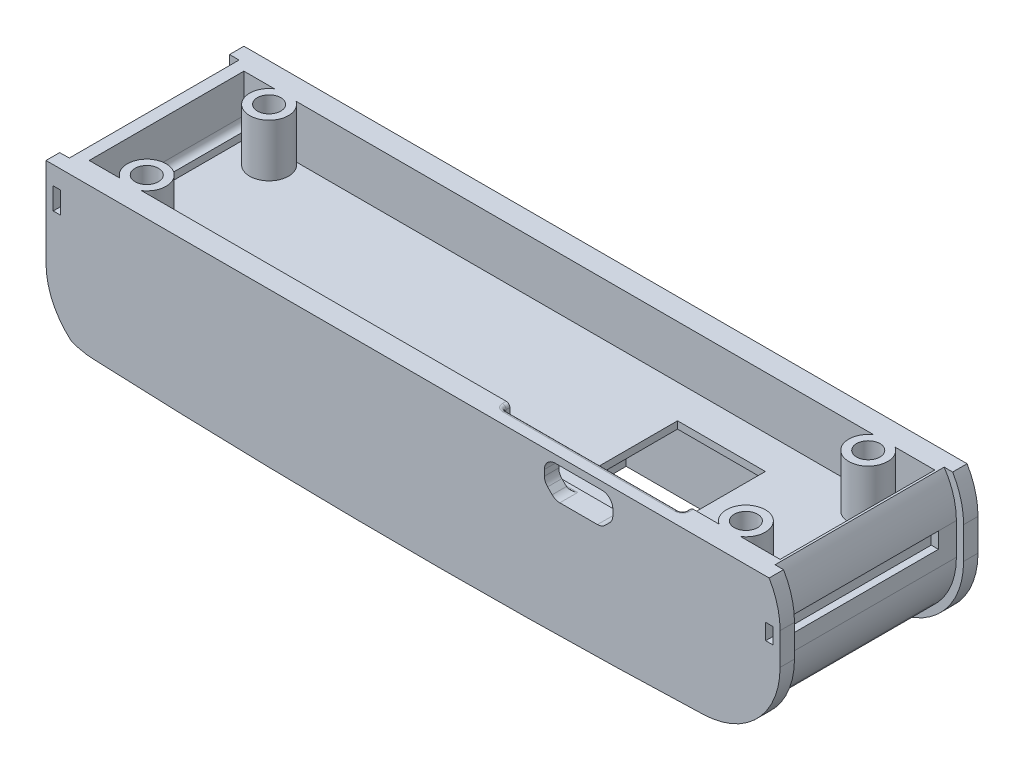
SolidWorks part; units mm, degrees
material "ABS"
ref_plane "Front" through (0, 0, 0) normal (0, 0, 1) x (1, 0, 0)
ref_plane "Top" through (0, 0, 0) normal (0, 1, 0) x (1, 0, 0)
ref_plane "Right" through (0, 0, 0) normal (1, 0, 0) x (0, 0, -1)
sketch "草图1" plane through (0, 0, 0) normal (0, 1, 0) x (1, 0, 0)
  line L0 (-48, 10.75) -> (-50, 10.75) construction
  line L6 (-48, 9.7892) -> (-48, -9.7108)
  line L12 (48, 9.7892) -> (48, -9.7108)
  line L13 (-48, 10.75) -> (48, -10.75) construction
  line L14 (-48, -10.75) -> (43.5349, 9.75) construction
  line L15 (-50, 12.75) -> (50, 12.75)
  line L16 (-50, 12.75) -> (-50, -12.75)
  line L17 (-50, -12.75) -> (50, -12.75)
  line L18 (50, 12.75) -> (50, -12.75)
  line L19 (-50, 12.75) -> (50, -12.75) construction
  line L20 (-50, -12.75) -> (-38.2259, -9.7476) construction
  line L21 (-48, 10.75) -> (-48, 12.75) construction
  line L24 (-48, 9.7892) -> (-48, 10.75)
  line L25 (-48, 10.75) -> (45.2523, 10.75)
  line L26 (45.2523, -13.75) -> (45.2523, 13.75) construction
  line L27 (48, 10.75) -> (-48, 10.75) construction
  line L29 (-48, -9.7108) -> (-48, -10.75)
  line L30 (-48, -10.75) -> (48, -10.75)
  line L31 (48, -10.75) -> (48, -9.7108)
  line L32 (0, 0) -> (42.1569, 10.75) construction
  line L33 (45.2523, 10.75) -> (48, 10.75)
  line L34 (48, 10.75) -> (48, 9.7892)
  point P0 (0, 0)
  point P6 (0, 0)
  dimension "D3" = 96
extrude "凸台-拉伸1" add sketch "草图1" along normal blind 13.2
sketch "草图2" plane through (0, 13.2, 0) normal (0, 1, 0) x (1, 0, 0)
  line L0 (-48, 0) -> (-23, 0) construction
  line L1 (-48, 10.75) -> (48, 10.75)
  line L2 (-48, 10.75) -> (-48, -10.75)
  line L3 (-48, -10.75) -> (48, -10.75)
  line L4 (48, 10.75) -> (48, -10.75)
  line L5 (-48, 10.75) -> (48, -10.75) construction
  line L6 (-48, -10.75) -> (48, 10.75) construction
  line L7 (17, 6) -> (29, 6)
  line L8 (17, 6) -> (17, -6)
  line L9 (17, -6) -> (29, -6)
  line L10 (29, 6) -> (29, -6)
  line L11 (-6, 6) -> (6, -6) construction
  line L12 (-6, -6) -> (6, 6) construction
  line L13 (0, 0) -> (23, 0) construction
  point P0 (0, 0)
  point P7 (0, 0)
  point P8 (0, 0)
  dimension "D1" = 12
extrude "凸台-拉伸2" add sketch "草图2" against normal blind 2
sketch "草图3" plane through (0, 13.2, 0) normal (0, 1, 0) x (1, 0, 0)
  line L0 (0, 0) -> (-50, 0) construction
  line L1 (-50, 12.75) -> (-50, -12.75) construction
  line L2 (-50, -12.75) -> (-50, 12.75)
  line L3 (-50, 12.75) -> (50, 12.75)
  line L4 (50, 12.75) -> (50, -0.0404)
  line L5 (50, -12.75) -> (50, 12.75) construction
  line L7 (48, 0.0137) -> (48, 10.75)
  line L8 (48, 10.75) -> (-48, 10.75)
  line L9 (-48, 10.75) -> (-48, -10.75)
  line L10 (48, -10.75) -> (-48, -10.75)
  line L11 (48, 0.0137) -> (48, -10.75)
  line L13 (50, -12.75) -> (50, -0.0404)
  line L14 (-50, -12.75) -> (50, -12.75)
  line L15 (48, 10.75) -> (-48, 10.75) construction
  line L16 (-48, 10.75) -> (-48, -10.75) construction
  line L17 (48, -10.75) -> (48, 10.75) construction
  point P17 (-48, 0)
extrude "凸台-拉伸3" add sketch "草图3" along normal blind 6.3
sketch "草图6" plane through (0, 19.5, 0) normal (0, 1, 0) x (1, 0, 0)
  line L6 (0, 0) -> (0, -19.5291) construction
  line L7 (-23, 6) -> (41, 6) construction
  line L8 (-32.25, -8.5) -> (29.1938, -8.5) construction
  line L9 (-32.25, 8.5) -> (39.5985, 8.5) construction
  line L10 (-50, 0) -> (0, 0) construction
  circle A4 centre (41, 8.5) radius 2.7
  circle A5 centre (41, -8.5) radius 2.7
  circle A6 centre (-42.25, -8.5) radius 2.7
  circle A7 centre (-42.25, 8.5) radius 2.7
extrude "凸台-拉伸4" add sketch "草图6" against normal up to next
sketch "草图7" plane through (0, 19.5, 0) normal (0, 1, 0) x (1, 0, 0)
  line L0 (0, 12.75) -> (0, 0) construction
  line L1 (0, 0) -> (-50, 0) construction
  line L4 (50, 12.75) -> (-50, 12.75) construction
  circle A4 centre (41, 8.5) radius 1.625
  circle A5 centre (41, -8.5) radius 1.625
  circle A6 centre (-42.25, -8.5) radius 1.625
  circle A7 centre (-42.25, 8.5) radius 1.625
  dimension "D1" = 83.25
extrude "切除-拉伸3" cut sketch "草图7" against normal blind 5.5
sketch "草图10" plane through (0, 11.2, 0) normal (0, -1, 0) x (1, 0, 0)
  line L0 (-23, 0) -> (23, 0) construction
  line L1 (15.9, 7.1) -> (30.1, 7.1)
  line L2 (15.9, 7.1) -> (15.9, -7.1)
  line L3 (15.9, -7.1) -> (30.1, -7.1)
  line L4 (30.1, 7.1) -> (30.1, -7.1)
  line L5 (15.9, 7.1) -> (30.1, -7.1) construction
  line L6 (15.9, -7.1) -> (30.1, 7.1) construction
  line L7 (15.1, 7.9) -> (30.9, 7.9)
  line L8 (15.1, 7.9) -> (15.1, -7.9)
  line L9 (15.1, -7.9) -> (30.9, -7.9)
  line L10 (30.9, 7.9) -> (30.9, -7.9)
  line L11 (15.1, 7.9) -> (30.9, -7.9) construction
  line L12 (15.1, -7.9) -> (30.9, 7.9) construction
  point P0 (23, 0)
  dimension "D1" = 14.2
  dimension "D2" = 0.8
extrude "凸台-拉伸5" add sketch "草图10" along normal blind 0.8 contours L10 L7 L8 L9 L1 L4 L3 L2 region at (23, 11.2, 7.6766)
sketch "草图11" plane through (0, 0, 12.75) normal (0, 0, 1) x (1, 0, 0)
  line L0 (0, 0) -> (0, 19.5) construction
  line L1 (-4, 17.65) -> (4, 17.65)
  line L2 (4, 17.65) -> (4, 15.8)
  line L3 (4, 15.8) -> (3, 14.8)
  line L4 (3, 14.8) -> (-3, 14.8)
  line L5 (-4, 15.8) -> (-3, 14.8)
  line L6 (-4, 17.65) -> (-4, 15.8)
  line L7 (-50, 19.5) -> (50, 19.5) construction
  line L8 (-39.5075, 13.2) -> (30.7575, 13.2) construction
  point P7 (0, 14.8)
  point P9 (0, 17.65)
  dimension "D1" = 8
  dimension "D2" = 135
  dimension "D3" = 1
  dimension "D4" = 1.6
  dimension "D5" = 2.85
extrude "切除-拉伸5" cut sketch "草图11" against normal blind 3
fillet "圆角6" radius 0.5 6 edges at (4, 15.8, 11.75) (3, 14.8, 11.75) (-3, 14.8, 11.75) (-4, 15.8, 11.75) (-4, 17.65, 11.75) (4, 17.65, 11.75)
fillet "圆角3" radius 0.95 2 edges at (-48, 13.2, 0) (48, 13.2, 0)
fillet "圆角1" radius 2 4 edges at (50, 9.75, -12.75) (-50, 9.75, 12.75) (50, 9.75, 12.75) (-50, 9.75, -12.75)
ref_plane "基准面3" through (0, 0, -10.75) normal (0, 0, -1) x (-1, 0, 0)
sketch "草图23" plane through (0, 0, -10.75) normal (0, 0, -1) x (-1, 0, 0)
  line L0 (-50, 19.5) -> (-50, -0.5)
  line L5 (-48, 19.5) -> (-50, 19.5) construction
  line L6 (-50, -0.5) -> (51, -0.5)
  line L7 (51, -0.5) -> (51, 19.5)
  line L8 (51, 19.5) -> (-50, 19.5)
sketch "草图18" plane through (0, 19.5, 0) normal (0, 1, 0) x (1, 0, 0)
  line L0 (-48, -12.75) -> (-53, -12.75)
  line L1 (-53, 26) -> (-53, -26) construction
  line L2 (-53, -12.75) -> (-53, -11.8645)
  line L6 (-37.0111, -11.75) -> (-37.0111, -12.75)
  line L7 (-48, -12.75) -> (48, -12.75) construction
  line L8 (-37.0111, -12.75) -> (-48, -12.75)
  line L9 (-37.0111, 11.75) -> (-37.0111, 12.75)
  line L11 (48, 12.75) -> (-48, 12.75) construction
  line L12 (-37.0111, 12.75) -> (-53, 12.75)
  line L13 (-53, 12.75) -> (-53, 11.75)
  line L15 (-53, -11.8645) -> (-37.0111, -11.75)
  line L16 (-53, 11.75) -> (-37.0111, 11.75)
extrude "凸台-拉伸7" add sketch "草图18" against normal blind 20
sketch "草图19" plane through (-53, 0, 0) normal (-1, 0, 0) x (0, 0, 1)
  line L0 (11.8736, -0.5079) -> (26.8736, -0.5079)
  line L1 (26.8736, -0.5079) -> (26.8736, 19.4921)
  line L2 (26.8736, 19.4921) -> (11.8736, 19.4921)
  line L3 (11.8736, 19.4921) -> (11.8736, -0.5079)
  line L4 (-11.75, -0.5) -> (-26.75, -0.5)
  line L5 (-12.75, -0.5) -> (-11.75, -0.5) construction
  line L6 (-11.75, -0.5) -> (-11.75, 19.5) construction
  line L7 (-26.75, -0.5) -> (-26.75, 19.5)
  line L8 (-26.75, 19.5) -> (-11.75, 19.5)
  line L9 (-11.75, 19.5) -> (-11.75, -0.5)
extrude "凸台-拉伸8" add sketch "草图19" against normal blind 2
sketch "草图20" plane through (-53, 0, 0) normal (-1, 0, 0) x (0, 0, 1)
  line L0 (0, 13.9) -> (0, -6.4084) construction
  line L1 (0, 54.2543) -> (0, -9.2543) construction
  line L2 (11.8736, -0.5079) -> (26.8736, -0.5079) construction
  circle A0 centre (20, 11.9921) radius 1.55
  circle A1 centre (-20, 11.9921) radius 1.55
  dimension "D1" = 40
  dimension "D2" = 12.5
extrude "切除-拉伸8" cut sketch "草图20" against normal blind 2
sketch "草图21" plane through (0, 0, -11.75) normal (0, 0, 1) x (1, 0, 0)
  line L1 (-50, 11.869) -> (-50, 16.9603)
  line L5 (-57.0725, 46.2563) -> (-50, 11.869)
  line L6 (-33.7407, 53.4984) -> (-57.0725, 46.2563)
  line L7 (-49.0355, 21.245) -> (-33.7407, 53.4984)
  arc A1 (-49.0355, 21.245) -> (-50, 16.9603) centre (-40, 16.9603) ccw
sketch "草图22" plane through (0, 0, 12.75) normal (0, 0, 1) x (1, 0, 0)
  line L0 (45.2523, 22.4304) -> (34.9699, 28.7768)
  line L1 (-31.6973, 69.925) -> (45.1395, 22.5) construction
  line L2 (50, 13.9208) -> (50, 4.3791)
  line L3 (50, 4.3791) -> (55.1917, 10.9989)
  line L4 (55.1917, 10.9989) -> (47.2062, 26.2201)
  line L5 (47.2062, 26.2201) -> (34.9699, 28.7768)
  arc A0 (45.2523, 22.4304) -> (50, 13.9208) centre (40, 13.9208) cw
  point P8 (50, 19.5)
  dimension "D1" = 10
extrude "凸台-拉伸13" add sketch "草图23" along normal blind 3 contours L0 L6 L7 L8
sketch "草图24" plane through (0, 0, 10.75) normal (0, 0, -1) x (-1, 0, 0)
  line L1 (-50, 19.5) -> (51, 19.5)
  line L2 (-50, 19.5) -> (-50, -0.5)
  line L3 (-50, -0.5) -> (51, -0.5)
  line L4 (51, 19.5) -> (51, -0.5)
extrude "凸台-拉伸15" add sketch "草图24" against normal blind 3
sketch "草图25" plane through (0, 0, -11.75) normal (0, 0, 1) x (1, 0, 0)
  line L6 (-38.7381, -0.4978) -> (-51.3208, -1.77)
  line L7 (-51.4889, 1.3597) -> (-50, 19.5)
  line L8 (-51.3208, -1.77) -> (-51.4889, 1.3597)
  line L9 (-50, 19.5) -> (-50, 9.5596)
  line L11 (50, 19.5) -> (55.4643, -8.4655)
  line L12 (50, 19.5) -> (50, 9.5765)
  arc A3 (-40.4019, -0.4323) -> (-50, 9.5596) centre (-40, 9.5596) cw
  arc A4 (50, 9.5765) -> (40.4061, -0.4153) centre (40, 9.5765) cw
  arc A5 (-40.4019, -0.4323) -> (-38.7381, -0.4978) centre (-0.2081, 998.7596) ccw
extrude "切除-拉伸13" cut sketch "草图22" against normal mid plane 80
extrude "切除-拉伸14" cut sketch "草图21" along normal up to surface (23.4766 mm away) up to face at (-52, 9.5, 11.8574)
extrude "切除-拉伸15" cut sketch "草图25" along normal up to surface (23.5243 mm away) contours L6 L8 L7 L9 A3 A5 up to face at (-51.1077, 11.9387, 11.851)
sketch "草图26" plane through (0, 0, -11.75) normal (0, 0, 1) x (1, 0, 0)
  line L0 (-51.0483, 18.4275) -> (-51.8061, 12.9844)
  line L1 (-51.8061, 12.9844) -> (-50.9317, 5.1015)
  line L2 (-50.9317, 5.1015) -> (-50.2088, 15.1871)
  line L3 (-50.2088, 15.1871) -> (-51.0483, 18.4275)
extrude "切除-拉伸16" cut sketch "草图26" along normal up to surface (23.5997 mm away) up to face at (-50.8159, 12.6978, 11.8489)
sketch "草图27" plane through (0, 0, -13.75) normal (0, 0, -1) x (-1, 0, 0)
  line L0 (-50, 9.8308) -> (-50, 9.5)
  line L1 (-50, 13.9208) -> (-50, -0.5) construction
  line L2 (-40, -0.5) -> (-39.276, -0.5)
  line L3 (-50, -0.5) -> (51, -0.5) construction
  line L4 (-39.276, -0.5) -> (-53.1302, -4.8854)
  line L5 (-53.1302, -4.8854) -> (-50, 9.8308)
  arc A0 (-50, 9.5) -> (-40, -0.5) centre (-40, 9.5) ccw
  point P11 (-50, -0.5)
  dimension "D1" = 10
extrude "切除-拉伸17" cut sketch "草图27" against normal up to surface (27.5 mm away) up to face at (-0.7142, 11.9233, 13.75)
sketch "草图29" plane through (0, 0, 13.75) normal (0, 0, 1) x (1, 0, 0)
  line L0 (51, 9.5) -> (51, 13.9208)
  line L1 (48.2989, 19.5) -> (49.4801, 19.5)
  line L3 (48.2989, 19.5) -> (4.9263, 6.9163)
  line L4 (4.9263, 6.9163) -> (-47.4572, -0.5)
  line L5 (40, -0.5) -> (-51, -0.5) construction
  arc A2 (51, 13.9208) -> (49.4801, 19.5) centre (40, 13.9208) ccw
  arc A4 (40.3393, -1.4948) -> (-44.3288, -1.12) centre (2.6099, 1039.0132) cw
  arc A5 (-47.4572, -0.5) -> (-44.3288, -1.12) centre (-43.9952, 8.7656) ccw
  arc A7 (40.3393, -1.4948) -> (51, 9.5) centre (40, 9.5) ccw
extrude "凸台-拉伸16" add sketch "草图29" against normal blind 2
sketch "草图30" plane through (0, 0, -13.75) normal (0, 0, -1) x (-1, 0, 0)
  line L5 (-4.9263, 6.9163) -> (47.4572, -0.5)
  line L6 (-48.2989, 19.5) -> (-4.9263, 6.9163)
  line L7 (-48.2989, 19.5) -> (-49.4801, 19.5)
  line L8 (-51, 9.5) -> (-51, 13.9208)
  arc A4 (-40.3393, -1.4948) -> (-51, 9.5) centre (-40, 9.5) cw
  arc A5 (47.4572, -0.5) -> (44.3288, -1.12) centre (43.9952, 8.7656) cw
  arc A6 (-40.3393, -1.4948) -> (44.3288, -1.12) centre (-2.6099, 1039.0132) ccw
  arc A7 (-51, 13.9208) -> (-49.4801, 19.5) centre (-40, 13.9208) cw
extrude "凸台-拉伸17" add sketch "草图30" against normal up to surface (2 mm away) up to face at (-46.958, 7.7086, -11.75)
sketch "草图32" plane through (0, 0, 13.75) normal (0, 0, 1) x (1, 0, 0)
  line L0 (-6.9911, 19.4921) -> (23.0089, 19.4921) construction
  line L1 (-0.07, 18.45) -> (-23, 18.45) construction
  line L2 (23.0089, 18.45) -> (69.0089, 18.45) construction
  line L18 (18.259, 16.95) -> (18.259, 16.1329)
  line L19 (18.6983, 15.0722) -> (19.3312, 14.4394)
  line L20 (20.3918, 14) -> (25.626, 14)
  line L21 (26.6867, 14.4394) -> (27.3195, 15.0722)
  line L22 (27.7589, 16.1329) -> (27.7589, 16.95)
  line L23 (26.2589, 18.45) -> (19.759, 18.45)
  arc A18 (19.759, 18.45) -> (18.259, 16.95) centre (19.759, 16.95) ccw
  arc A19 (18.259, 16.1329) -> (18.6983, 15.0722) centre (19.759, 16.1329) ccw
  arc A20 (19.3312, 14.4394) -> (20.3918, 14) centre (20.3918, 15.5) ccw
  arc A21 (25.626, 14) -> (26.6867, 14.4394) centre (25.626, 15.5) ccw
  arc A22 (27.3195, 15.0722) -> (27.7589, 16.1329) centre (26.2589, 16.1329) ccw
  arc A23 (27.7589, 16.95) -> (26.2589, 18.45) centre (26.2589, 16.95) ccw
extrude "切除-拉伸18" cut sketch "草图32" against normal blind 10
sketch "草图33" plane through (50, 0, 0) normal (1, 0, 0) x (0, 0, -1)
  line L1 (9.25, 13.9208) -> (-9.25, 13.9208)
  line L3 (9.25, 11.7104) -> (-9.25, 11.7104)
  line L5 (9.25, 13.9208) -> (9.25, 11.7104)
  line L6 (-9.25, 13.9208) -> (-9.25, 11.7104)
extrude "切除-拉伸19" cut sketch "草图33" against normal blind 1
sketch "草图34" plane through (0, 0, 13.75) normal (0, 0, 1) x (1, 0, 0)
  line L0 (49, 13.9208) -> (49, 11.7104) construction
  line L1 (49, 13.9208) -> (50, 13.9208) construction
  line L2 (50, 9.5) -> (50, 13.9208) construction
  line L3 (49, 11.7104) -> (50, 11.7104) construction
  line L4 (49, 13.9208) -> (49, 11.7104)
  line L5 (49, 13.9208) -> (50, 13.9208)
  line L6 (50, 11.7104) -> (50, 13.9208)
  line L7 (49, 11.7104) -> (50, 11.7104)
extrude "切除-拉伸20" cut sketch "草图34" against normal blind 10 contours L6 L5 L4 L7
sketch "草图35" plane through (-50, 0, 0) normal (-1, 0, 0) x (0, 0, 1)
  line L1 (-9.25, 13.9208) -> (-9.25, 16.9603)
  line L2 (11.843, 16.9603) -> (-9.25, 16.9603)
  line L3 (11.843, 16.9603) -> (11.843, 16.95)
  line L4 (11.843, 13.9208) -> (-9.25, 13.9208)
  line L6 (11.843, 13.9208) -> (13.75, 13.9208)
  line L8 (11.843, 16.95) -> (13.75, 16.95)
  line L9 (13.75, 13.9208) -> (13.75, 16.95)
extrude "切除-拉伸21" cut sketch "草图35" against normal blind 1
sketch "草图38" plane through (-51, 0, 0) normal (1, 0, 0) x (0, 0, -1)
  line L1 (-28.1477, 20.2918) -> (28.6102, 20.2918)
  line L2 (-28.1477, 20.2918) -> (-28.1477, -1.8433)
  line L3 (-28.1477, -1.8433) -> (28.6102, -1.8433)
  line L4 (28.6102, 20.2918) -> (28.6102, -1.8433)
extrude "切除-拉伸25" cut sketch "草图38" against normal blind 10
fillet "圆角7" radius 10 2 edges at (-51, -0.5, -12.75) (-51, -0.5, 12.8001)
sketch "草图41" plane through (0, 11.2, 0) normal (0, -1, 0) x (1, 0, 0)
  line L1 (-48, 10.75) -> (-38.7596, 10.75)
  line L2 (-48, 10.75) -> (-48, -10.75)
  line L3 (-48, -10.75) -> (-38.7596, -10.75)
  line L4 (-38.7596, 10.75) -> (-38.7596, -10.75)
  line L5 (48, 10.75) -> (40, 10.75)
  line L6 (48, 10.75) -> (48, -10.75)
  line L7 (48, -10.75) -> (40, -10.75)
  line L8 (40, 10.75) -> (40, -10.75)
extrude "凸台-拉伸19" add sketch "草图41" along normal blind 11.69
fillet "圆角8" radius 10 2 edges at (48, -0.49, 0) (-48, -0.49, 0)
sketch "草图42" plane through (0, 13.2, 0) normal (0, 1, 0) x (1, 0, 0)
  line L0 (-23, 0) -> (23, 0) construction
  line L1 (16.9, -6.1) -> (29.1, -6.1)
  line L2 (16.9, -6.1) -> (16.9, 6.1)
  line L3 (16.9, 6.1) -> (29.1, 6.1)
  line L4 (29.1, -6.1) -> (29.1, 6.1)
  line L5 (16.9, -6.1) -> (29.1, 6.1) construction
  line L6 (-29.1, 6.1) -> (-16.9, -6.1) construction
  point P0 (23, 0)
  point P6 (23, 0)
extrude "切除-拉伸26" cut sketch "草图42" against normal blind 10
sketch "草图43" plane through (0, 19.5, 0) normal (0, 1, 0) x (1, 0, 0)
  line L0 (10.4494, -10.328) -> (35.4494, -10.328)
  line L1 (22.9494, -10.7606) -> (68.9494, -10.7725) construction
  line L2 (35.4494, -10.328) -> (35.4494, -11.7606)
  line L3 (35.4494, -11.7606) -> (10.4494, -11.7606)
  line L4 (10.4494, -11.7606) -> (10.4494, -10.328)
  line L5 (10.4494, -10.328) -> (35.4494, -10.328)
  line L6 (22.9494, -6.1225) -> (22.9494, -10.7606) construction
extrude "切除-拉伸28" cut sketch "草图43" against normal up to surface (5.5 mm away) contours L4 L3 L2 region at (22.9494, 19.5, 11.0443) up to face at (23.0089, 14, 12.25)
fillet "圆角9" radius 0.5 7 edges at (22.9494, 19.5, 11.7606) (35.4494, 16.75, 11.7606) (10.4494, 16.75, 11.7606) (10.4494, 19.5, 11.2553) (35.4494, 19.5, 11.2553) (35.4494, 14, 11.2553) (10.4494, 14, 11.2553)
fillet "圆角10" radius 0.5 4 edges at (35.3029, 14.1465, 11.6142) (10.5958, 14.1465, 11.6142) (30.2877, 14, 11.7606) (15.6706, 14, 11.7606)
ref_plane "基准面4" through (23, 0, 0) normal (1, 0, 0) x (0, 0, -1)
sketch "草图44" plane through (0, 11.2, 0) normal (0, -1, 0) x (1, 0, 0)
  line L0 (23, 0) -> (-7, 0) construction
  line L1 (23, -1.1) -> (23, 1.1) construction
  line L2 (23, 0) -> (6, 0) construction
  line L3 (-38.7596, 10.75) -> (6.122, 10.75)
  line L4 (-38.7596, 10.75) -> (-38.7596, -10.75)
  line L5 (-38.7596, -10.75) -> (6.122, -10.75)
  line L6 (6.122, 10.75) -> (6.122, -10.75)
  line L7 (-38.7596, -10.75) -> (-38.7596, 10.75) construction
  point P12 (-38.7596, 0)
extrude "凸台-拉伸20" add sketch "草图44" along normal up to surface (11.7 mm away) up to face at (0.6202, -0.5, 11.25)
sketch "草图45" plane through (0, 0, 10.75) normal (0, 0, -1) x (-1, 0, 0)
  line L1 (-6.122, -0.5) -> (-40, -0.5)
  line L2 (-6.122, -0.5) -> (-6.122, 11.2)
  line L3 (-6.122, 11.2) -> (-40, 11.2)
  line L4 (-40, -0.5) -> (-40, 11.2)
extrude "凸台-拉伸21" add sketch "草图45" along normal blind 1
sketch "草图46" plane through (0, 0, -10.75) normal (0, 0, 1) x (1, 0, 0)
  line L0 (6.122, -0.5) -> (6.122, 11.2) construction
  line L1 (40, -0.5) -> (6.122, -0.5)
  line L2 (40, -0.5) -> (40, 11.2)
  line L3 (40, 11.2) -> (6.122, 11.2)
  line L4 (6.122, -0.5) -> (6.122, 11.2)
  line L5 (40, 11.2) -> (6.122, 11.2) construction
extrude "凸台-拉伸22" add sketch "草图46" along normal blind 1
sketch "草图47" plane through (0, 13.2, 0) normal (0, 1, 0) x (1, 0, 0)
  line L1 (-47.05, 10.75) -> (47.05, 10.75)
  line L2 (-47.05, 10.75) -> (-47.05, -10.75)
  line L3 (-47.05, -10.75) -> (47.05, -10.75)
  line L4 (47.05, 10.75) -> (47.05, -10.75)
  arc A0 (42.4925, -10.75) -> (39.5075, -10.75) centre (41, -8.5) ccw construction
  arc A1 (39.5075, 10.75) -> (42.4925, 10.75) centre (41, 8.5) ccw construction
  arc A2 (-40.7575, -10.75) -> (-43.7425, -10.75) centre (-42.25, -8.5) ccw construction
  arc A3 (-43.7425, 10.75) -> (-40.7575, 10.75) centre (-42.25, 8.5) ccw construction
  arc A4 (42.4925, -10.75) -> (39.5075, -10.75) centre (41, -8.5) ccw
  arc A5 (39.5075, 10.75) -> (42.4925, 10.75) centre (41, 8.5) ccw
  arc A6 (-40.7575, -10.75) -> (-43.7425, -10.75) centre (-42.25, -8.5) ccw
  arc A7 (-43.7425, 10.75) -> (-40.7575, 10.75) centre (-42.25, 8.5) ccw
  line M1 (29.1, 6.1) -> (29.1, -6.1)
  line M2 (29.1, -6.1) -> (16.9, -6.1)
  line M3 (16.9, -6.1) -> (16.9, 6.1)
  line M4 (16.9, 6.1) -> (29.1, 6.1)
  line M5 (-43.7425, 10.75) -> (-47.05, 10.75)
  line M6 (-47.05, 10.75) -> (-47.05, -10.75)
  line M7 (-47.05, -10.75) -> (-43.7425, -10.75)
  arc M8 (-43.7425, -10.75) -> (-40.7575, -10.75) centre (-42.25, -8.5) cw
  line M9 (-40.7575, -10.75) -> (39.5075, -10.75)
  arc M10 (39.5075, -10.75) -> (42.4925, -10.75) centre (41, -8.5) cw
  line M11 (42.4925, -10.75) -> (47.05, -10.75)
  line M12 (47.05, -10.75) -> (47.05, 10.75)
  line M13 (47.05, 10.75) -> (42.4925, 10.75)
  arc M14 (42.4925, 10.75) -> (39.5075, 10.75) centre (41, 8.5) cw
  line M15 (39.5075, 10.75) -> (-40.7575, 10.75)
  arc M16 (-40.7575, 10.75) -> (-43.7425, 10.75) centre (-42.25, 8.5) cw
extrude "切除-拉伸29" cut sketch "草图47" against normal blind 1 contours M16 M5 M6 M7 M8 M9 M10 M11 M12 M13 M14 M15 M4 M1 M2 M3 region at (-1.8856, 13.2, 0)
